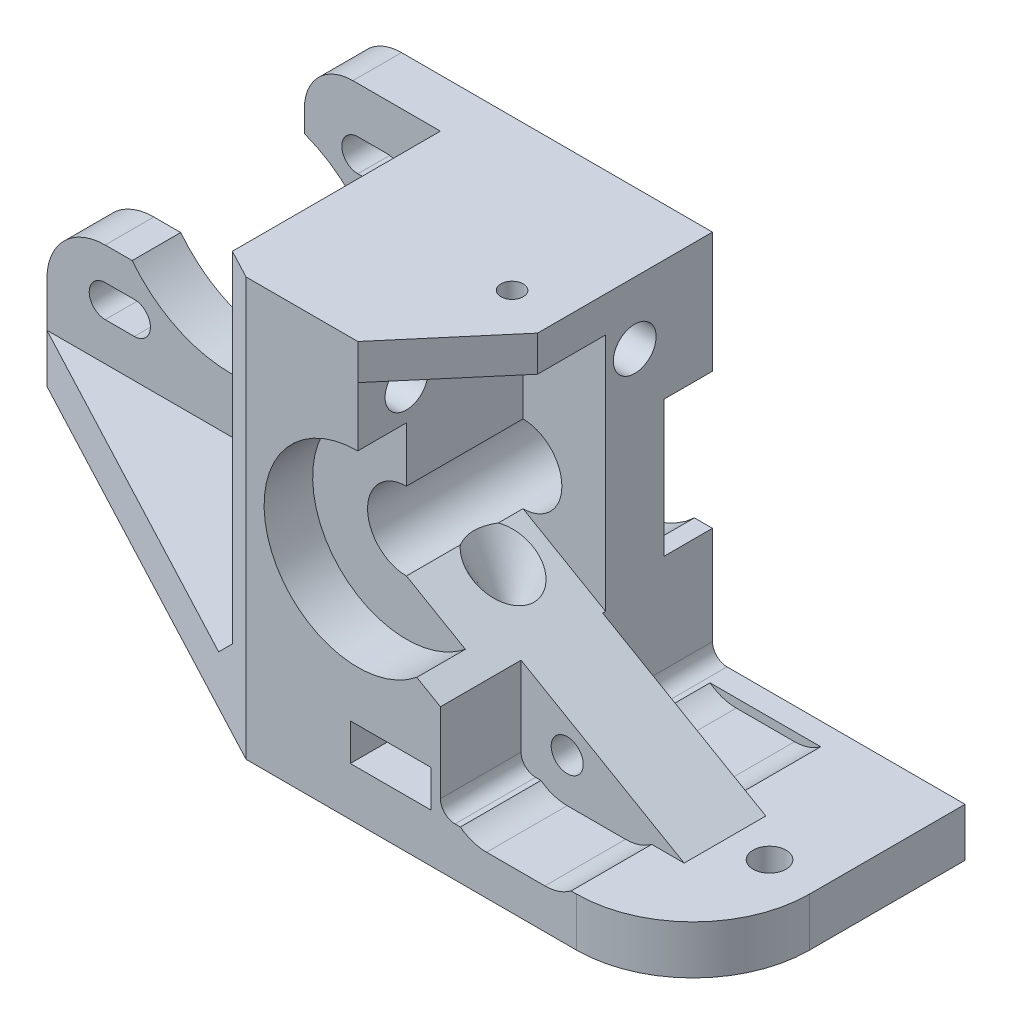
SolidWorks part; units mm, degrees
ref_plane "Front Plane" through (0, 0, 0) normal (0, 0, 1) x (1, 0, 0)
ref_plane "Top Plane" through (0, 0, 0) normal (0, 1, 0) x (1, 0, 0)
ref_plane "Right Plane" through (0, 0, 0) normal (1, 0, 0) x (0, 0, -1)
sketch "Sketch1" plane through (0, 0, 0) normal (0, 0, 1) x (1, 0, 0)
  line L0 (0, 0) -> (-60, 0) construction
  line L1 (-55, -23.6) -> (34.5, -23.6)
  line L2 (-55, -23.6) -> (-55, -8)
  line L3 (-28.5, 19.4) -> (34.5, 19.4)
  line L4 (34.5, -23.6) -> (34.5, 19.4)
  line L5 (-34.5, 0) -> (-34.5, -23.6) construction
  line L6 (-21.5, -17.6494) -> (-21.5, 14.65) construction
  line L7 (-20, 13) -> (-50, 13) construction
  line L8 (-23, 11.35) -> (-20, 11.35)
  line L9 (-23, 11.35) -> (-23, 14.65) construction
  line L10 (-23, 14.65) -> (-20, 14.65)
  line L11 (-20, 11.35) -> (-20, 14.65) construction
  line L12 (-36, -12.9851) -> (-33, -12.9851)
  line L14 (-20, -11.35) -> (-20, -14.65) construction
  line L15 (-23, -14.65) -> (-20, -14.65)
  line L16 (-23, -11.35) -> (-23, -14.65) construction
  line L17 (-23, -11.35) -> (-20, -11.35)
  line L18 (-46, -11.35) -> (-49, -11.35)
  line L19 (-46, -11.35) -> (-46, -14.65) construction
  line L20 (-46, -14.65) -> (-49, -14.65)
  line L21 (-49, -11.35) -> (-49, -14.65) construction
  line L26 (-28.5, 19.4) -> (-28.5, 12.1804)
  line L27 (-55, -8) -> (-46.228, -8)
  line L28 (-50, -13) -> (-19, -13) [skipped]
  line L29 (-47.5, 17.6494) -> (-47.5, -13.3506) [skipped]
  circle A0 centre (0, 0) radius 4
  circle A1 centre (-34.5, 0) radius 13 construction
  arc A2 (-46.228, -8) -> (-36, -12.9851) centre (-36, 0) ccw
  arc A3 (-20, 11.35) -> (-20, 14.65) centre (-20, 13) ccw
  arc A4 (-33, -12.9851) -> (-28.5, 12.1804) centre (-33, 0) ccw
  arc A5 (-23, 14.65) -> (-23, 11.35) centre (-23, 13) ccw
  arc A6 (-23, -11.35) -> (-23, -14.65) centre (-23, -13) ccw
  arc A7 (-20, -14.65) -> (-20, -11.35) centre (-20, -13) ccw
  arc A8 (-49, -11.35) -> (-49, -14.65) centre (-49, -13) ccw
  arc A9 (-46, -14.65) -> (-46, -11.35) centre (-46, -13) ccw
  dimension "D1" = 8
  dimension "D6" = 34.5
  dimension "D8" = 3.3
  dimension "D2" = 26
  dimension "D7" = 6
  dimension "D3" = 43
  dimension "D4" = 55
  dimension "D5" = 23.6
  dimension "D9" = 3
  dimension "D10" = 3
  dimension "D11" = 1.5
  dimension "D12" = 8
  dimension "D13" = 34.5
extrude "Boss-Extrude1" add sketch "Sketch1" along normal blind 28
sketch "Sketch2" plane through (0, 0, 28) normal (0, 0, 1) x (1, 0, 0)
  line L0 (-55, -8) -> (-55, -23.6) construction
  line L1 (-55, -18.6) -> (-14.5, -18.6)
  line L2 (-55, -18.6) -> (-55, 19.4)
  line L3 (-55, 19.4) -> (-14.5, 19.4)
  line L4 (-14.5, -18.6) -> (-14.5, 19.4)
  line L5 (34.5, 19.4) -> (-28.5, 19.4) construction
  line L6 (0, 0) -> (-55, 0) construction
  circle A0 centre (-34.5, 0) radius 17.3693 construction
  dimension "D1" = 20
  dimension "D2" = 18.6
  dimension "D3" = 34.5
extrude "Cut-Extrude1" cut sketch "Sketch2" against normal offset from surface (23 mm away) 5 up to face at (-21.5, -13, 0)
sketch "Sketch3" plane through (0, 0, 28) normal (0, 0, 1) x (1, 0, 0)
  circle A0 centre (0, 0) radius 9.65
  dimension "D1" = 19.3
extrude "Cut-Extrude2" cut sketch "Sketch3" against normal blind 5
ref_plane "Plane1" through (0, 0, 11) normal (0, 0, 1) x (1, 0, 0)
ref_plane "Plane2" through (0, -18.6, 0) normal (0, -1, 0) x (1, 0, 0)
ref_plane "Plane3" through (0, 0, 15.5) normal (0, 0, 1) x (1, 0, 0)
sketch "Sketch8" plane through (0, -23.6, 0) normal (0, -1, 0) x (1, 0, 0)
  circle A0 centre (3.375, 15.5) radius 1.15
  dimension "D1" = 2.3
  dimension "D2" = 3.375
  dimension "D3" = 15.5
extrude "Cut-Extrude7" cut sketch "Sketch8" against normal through all
chamfer "Chamfer1" distance 23 distance2 43.5 1 edges at (-55, -21.1, 28) first distance on face at (-55, -16.7333, 11)
sketch "Sketch9" plane through (34.5, 0, 0) normal (1, 0, 0) x (0, 0, -1)
  line L1 (-15.5, 23.65) -> (-15.5, -23.65) construction
  line L2 (0, 0) -> (-25.9492, 0) construction
  circle A0 centre (-8, 13) radius 2.2
  circle A1 centre (-23, 13) radius 2.2
  dimension "D1" = 4.4
  dimension "D2" = 7.5
  dimension "D3" = 13
  dimension "D4" = 7.5
extrude "Cut-Extrude8" cut sketch "Sketch9" against normal through all
sketch "Sketch10" plane through (-14.5, 0, 0) normal (-1, 0, 0) x (0, 0, 1)
  line L1 (5.1, 14.6743) -> (5.1, 11.3257)
  line L2 (5.1, 11.3257) -> (8, 9.6514)
  line L3 (8, 9.6514) -> (10.9, 11.3257)
  line L4 (10.9, 11.3257) -> (10.9, 14.6743)
  line L5 (10.9, 14.6743) -> (8, 16.3486)
  line L6 (8, 16.3486) -> (5.1, 14.6743)
  line L7 (25.9, 11.3257) -> (25.9, 14.6743)
  line L8 (25.9, 14.6743) -> (23, 16.3486)
  line L9 (23, 16.3486) -> (20.1, 14.6743)
  line L10 (20.1, 14.6743) -> (20.1, 11.3257)
  line L11 (20.1, 11.3257) -> (23, 9.6514)
  line L12 (23, 9.6514) -> (25.9, 11.3257)
  circle A0 centre (8, 13) radius 2.9 construction
  circle A1 centre (8, 13) radius 2.2 construction
  circle A2 centre (23, 13) radius 2.9 construction
  circle A5 centre (23, 13) radius 2.2 construction
  dimension "D1" = 5.8
extrude "Cut-Extrude9" cut sketch "Sketch10" against normal blind 4 and the other way blind 3
chamfer "Chamfer2" distance 3 angle 45 1 edges at (-14.5, -18.6, 15.7069)
sketch "Sketch16" plane through (0, 0, 28) normal (0, 0, 1) x (1, 0, 0)
  line L0 (-17.5, -18.6) -> (-55, -18.6) construction
  line L1 (34.5, 19.4) -> (8.5, 19.4)
  line L2 (34.5, 19.4) -> (34.5, -18.6)
  line L3 (34.5, -18.6) -> (8.5, -18.6)
  line L4 (8.5, 19.4) -> (8.5, -18.6)
  dimension "D1" = 8.5
extrude "Cut-Extrude12" cut sketch "Sketch16" against normal through all
sketch "Sketch4" plane through (0, 0, 0) normal (0, 0, -1) x (-1, 0, 0)
  line L0 (0, 0) -> (-36.3115, 0) construction
  line L1 (-36.3115, -7) -> (-6.6425, -7)
  line L2 (-36.3115, -7) -> (-36.3115, 7)
  line L4 (-36.3115, 7) -> (-6.6425, 7)
  line L5 (-36.3115, -7) -> (0, 5) construction
  line L6 (-1.3153, -8.4204) -> (-36.3115, 7) construction
  arc A0 (-6.6425, -7) -> (-6.6425, 7) centre (0, 0) ccw
  dimension "D1" = 19.3
  dimension "D2" = 14
extrude "Cut-Extrude3" cut sketch "Sketch4" against normal blind 5
fillet "Fillet6" radius 1.5 1 edges at (8.5, -18.6, 14)
sketch "Sketch17" plane through (0, 0, 28) normal (0, 0, 1) x (1, 0, 0)
  line L0 (8.5, 19.4) -> (8.5, 4.5686) construction
  line L1 (0, 0) -> (19.7064, 0) construction
  line L2 (0, 4) -> (0, -4) construction
  line L3 (0, 4) -> (0, 15.7335)
  line L4 (0, 15.7335) -> (8.5, 15.7335)
  line L6 (8.5, 15.7335) -> (8.5, -8.9075)
  line L7 (8.5, -8.9075) -> (0, -4)
  arc A2 (0, -4) -> (0, 4) centre (0, 0) ccw
  circle A4 centre (0, 0) radius 4 construction
  dimension "D1" = 120
extrude "Cut-Extrude13" cut sketch "Sketch17" against normal blind 17
ref_axis "Axis1" through (3.375, 19.4, 15.5) along (0, -1, 0)
sketch "Sketch20" plane through (0, 0, 15.5) normal (0, 0, 1) x (1, 0, 0)
  line L0 (3.375, -3.8) -> (3.375, -11.8) construction
  line L1 (3.375, 19.4) -> (3.375, 15.7335) construction
  line L2 (3.375, -11.8) -> (7.375, -3.8)
  line L3 (7.375, -3.8) -> (3.375, -3.8)
  line L4 (3.375, -3.8) -> (3.375, -11.8)
  dimension "D1" = 8
  dimension "D2" = 4
  dimension "D3" = 3.8
revolve "Cut-Revolve1" cut sketch "Sketch20" angle 360 mid plane about L0
sketch "Sketch21" plane through (0, 0, 15.5) normal (0, 0, 1) x (1, 0, 0)
  line L0 (14.7822, -11.8532) -> (7.25, -8.1858) construction
  line L1 (7.25, -8.1858) -> (7.25, -18.6)
  line L2 (7.25, -18.6) -> (25.2879, -18.6)
  line L3 (10, -18.6) -> (34.5, -18.6) construction
  line L4 (21.7997, -18.6) -> (15.7249, -12.5251) construction
  line L5 (6.0681, -7.5034) -> (8.5, -8.9075) construction
  line L6 (7.25, -8.1858) -> (25.2879, -18.6)
  line L7 (-15.4, -18.6) -> (15.4, -18.6) construction
  line L8 (0, -4) -> (6.0681, -7.5034) construction
  circle A0 centre (13.25, -15) radius 1.65
  arc A1 (15.7249, -12.5251) -> (14.7822, -11.8532) centre (13.25, -15) ccw construction
  dimension "D2" = 3.3
  dimension "D5" = 3.5
  dimension "D1" = 13.25
  dimension "D3" = 15
  dimension "D4" = 6
  dimension "D6" = 45
extrude "Boss-Extrude3" add sketch "Sketch21" against normal blind 4.2 and the other way blind 4.2
sketch "Sketch15" plane through (0, -23.6, 0) normal (0, -1, 0) x (1, 0, 0)
  line L0 (-20.625, 15) -> (29.375, 15) construction
  circle A1 centre (-20.625, 15) radius 1.7
  circle A2 centre (29.375, 15) radius 1.7
  circle A3 centre (3.375, 15.5) radius 1.15 construction
  point P4 (3.375, 15.5)
  dimension "D2" = 3.4
  dimension "D1" = 50
extrude "Cut-Extrude11" cut sketch "Sketch15" against normal through all
sketch "Sketch22" plane through (0, 0, 19.7) normal (0, 0, 1) x (1, 0, 0)
  line L0 (13.25, -19.5) -> (19.25, -19.5)
  line L3 (19.25, -10.5) -> (13.25, -10.5)
  arc A0 (13.25, -10.5) -> (13.25, -19.5) centre (13.25, -15) ccw
  circle A1 centre (13.25, -15) radius 1.65 construction
  arc A2 (19.25, -19.5) -> (19.25, -10.5) centre (19.25, -15) ccw
  dimension "D1" = 9
  dimension "D2" = 6
extrude "Cut-Extrude14" cut sketch "Sketch22" along normal blind 9
mirror "Mirror1" about plane through (0, 0, 15.5) normal (0, 0, 1) of "Cut-Extrude14"
chamfer "Chamfer4" distance 8.5 distance2 10 1 edges at (8.5, 17.5668, 28) first distance on face at (9.2891, -7.4521, 28)
fillet "Fillet1" radius 5 1 edges at (-28.5, 19.4, 2.5)
fillet "Fillet2" radius 6 1 edges at (-55, -8, 2.5)
fillet "Fillet4" radius 12 1 edges at (34.5, -21.1, 28)
sketch "Sketch23" plane through (0, -18.6, 0) normal (0, -1, 0) x (1, 0, 0)
  line L0 (-0.775, 28.722) -> (7.525, 28.722)
  line L3 (-0.775, 28.722) -> (-0.775, 13.104)
  line L4 (-0.775, 13.104) -> (3.375, 10.708)
  line L5 (3.375, 10.708) -> (7.525, 13.104)
  line L6 (7.525, 13.104) -> (7.525, 28.722)
  line L8 (3.375, 20.292) -> (-0.775, 17.896) [skipped]
  line L9 (7.525, 17.896) -> (3.375, 20.292) [skipped]
  circle A0 centre (3.375, 15.5) radius 4.25 construction
  dimension "D1" = 8.5
extrude "Cut-Extrude15" cut sketch "Sketch23" against normal blind 3.8
sketch "Sketch24" plane through (0, -23.6, 0) normal (0, -1, 0) x (1, 0, 0)
  line L0 (-10.475, 15.5) -> (17.225, 15.5) construction
  line L1 (23.65, 15.5) -> (-23.65, 15.5) construction
  circle A0 centre (3.375, 15.5) radius 12.5 construction
  circle A1 centre (-10.475, 15.5) radius 1.35
  circle A2 centre (17.225, 15.5) radius 1.35
  dimension "D1" = 25
  dimension "D2" = 2.7
extrude "Cut-Extrude16" [suppressed] cut sketch "Sketch24" against normal blind 10
sketch "Sketch25" [suppressed] plane through (0, -14.6, 0) normal (0, -1, 0) x (1, 0, 0)
  line L0 (-17.5, 18.4) -> (-17.5, 12.6)
  line L1 (20.125, 17.1743) -> (17.225, 18.8486)
  line L2 (17.225, 18.8486) -> (14.325, 17.1743)
  line L3 (14.325, 17.1743) -> (14.325, 13.8257)
  line L4 (14.325, 13.8257) -> (17.225, 12.1514)
  line L5 (17.225, 12.1514) -> (20.125, 13.8257)
  line L6 (20.125, 13.8257) -> (20.125, 17.1743)
  line L7 (-7.1264, 15.5) -> (-8.8007, 18.4)
  line L8 (-8.8007, 18.4) -> (-17.5, 18.4)
  line L9 (-17.5, 24.8276) -> (-17.5, 5) construction
  line L11 (-17.5, 12.6) -> (-8.8007, 12.6)
  line L12 (-8.8007, 12.6) -> (-7.1264, 15.5)
  line L14 (-13.8236, 15.5) -> (-12.1493, 12.6) [skipped]
  line L15 (-12.1493, 18.4) -> (-13.8236, 15.5) [skipped]
  circle A0 centre (17.225, 15.5) radius 2.9 construction
  circle A1 centre (-10.475, 15.5) radius 2.9 construction
  circle A2 centre (17.225, 15.5) radius 1.35 construction
  circle A3 centre (-10.475, 15.5) radius 1.35 construction
  dimension "D1" = 5.8
extrude "Cut-Extrude17" [suppressed] cut sketch "Sketch25" along normal blind 6 and the other way blind 3
sketch "Sketch26" plane through (0, -23.6, 0) normal (0, -1, 0) x (1, 0, 0)
  circle A0 centre (3.375, 15.5) radius 3.15
  circle A1 centre (3.375, 15.5) radius 1.15 construction
  dimension "D1" = 6.3
extrude "Cut-Extrude18" cut sketch "Sketch26" against normal up to next
